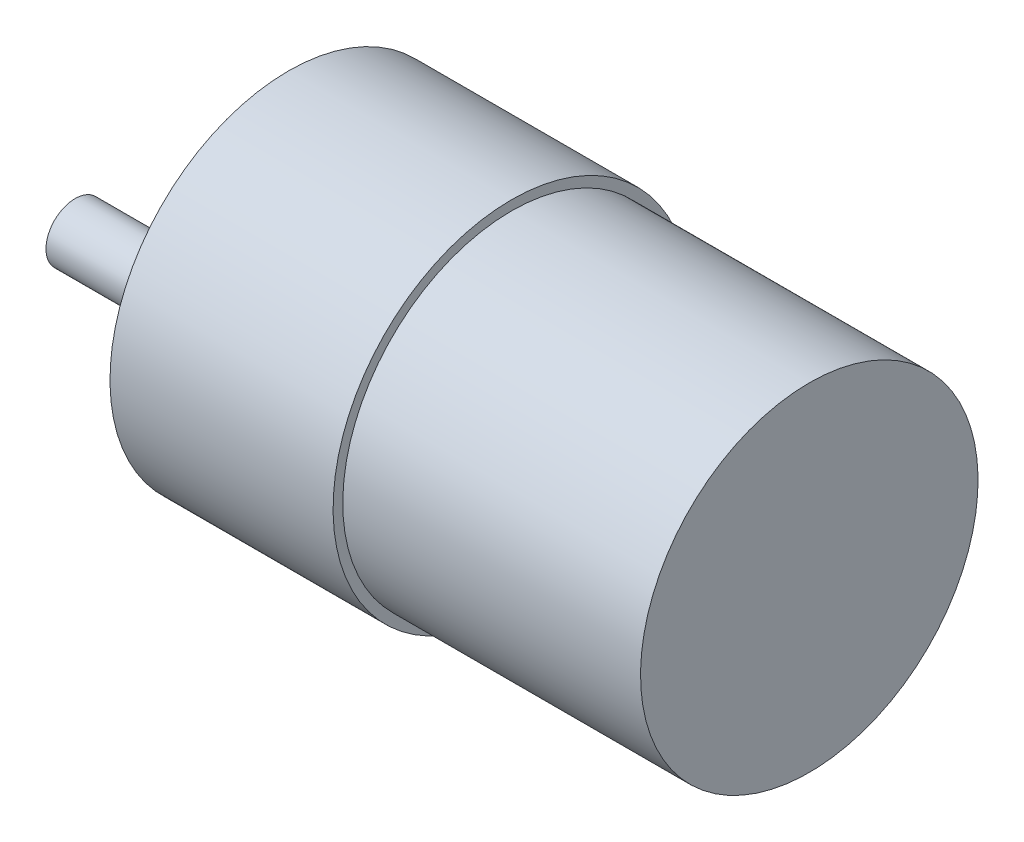
SolidWorks part; units mm, degrees
ref_plane "Front Plane" through (0, 0, 0) normal (0, 0, 1) x (1, 0, 0)
ref_plane "Top Plane" through (0, 0, 0) normal (0, 1, 0) x (1, 0, 0)
ref_plane "Right Plane" through (0, 0, 0) normal (1, 0, 0) x (0, 0, -1)
sketch "Sketch2" plane through (0, 0, 0) normal (0, 0, 1) x (1, 0, 0)
  line L0 (0, 0) -> (0, 18.4)
  line L1 (0, 18.4) -> (23, 18.4)
  line L2 (23, 18.4) -> (23, 17.4)
  line L3 (23, 17.4) -> (53.7, 17.4)
  line L4 (53.7, 17.4) -> (53.7, 0)
  line L5 (53.7, 0) -> (0, 0)
  dimension "D1" = 23
  dimension "D2" = 30.7
  dimension "D3" = 18.4
  dimension "D4" = 17.4
revolve "Revolve1" add sketch "Sketch2" angle 360 about L5
sketch "Sketch3" plane through (0, 0, 0) normal (-1, 0, 0) x (0, 0, 1)
  circle A0 centre (0, -7) radius 6
  circle A1 centre (0, -7) radius 3
  point P4 (-2.9081, -6.3673)
  dimension "D2" = 12
  dimension "D3" = 6
  dimension "D1" = 7
extrude "Boss-Extrude1" add sketch "Sketch3" along normal blind 22 contours A1
extrude "Boss-Extrude2" add sketch "Sketch3<3>" along normal blind 6 contours A0
sketch "Sketch3<3>" plane through (0, 0, 0) normal (-1, 0, 0) x (0, 0, 1) same geometry as "Sketch3"
sketch "Sketch4" plane through (0, 0, 0) normal (-1, 0, 0) x (0, 0, 1)
  circle A0 centre (15.5, 0) radius 1.5
  circle A1 centre (7.75, -13.4234) radius 1.5
  circle A2 centre (-7.75, -13.4234) radius 1.5
  circle A3 centre (-15.5, 0) radius 1.5
  circle A4 centre (-7.75, 13.4234) radius 1.5
  circle A5 centre (7.75, 13.4234) radius 1.5
  point P2 (0, 0)
  point P3 (15.4181, -1.5911)
  point P15 (0, 0)
  dimension "D3" = 3
  dimension "D2" = 31
  dimension "D1" = 6
extrude "Cut-Extrude1" cut sketch "Sketch4" against normal blind 6
